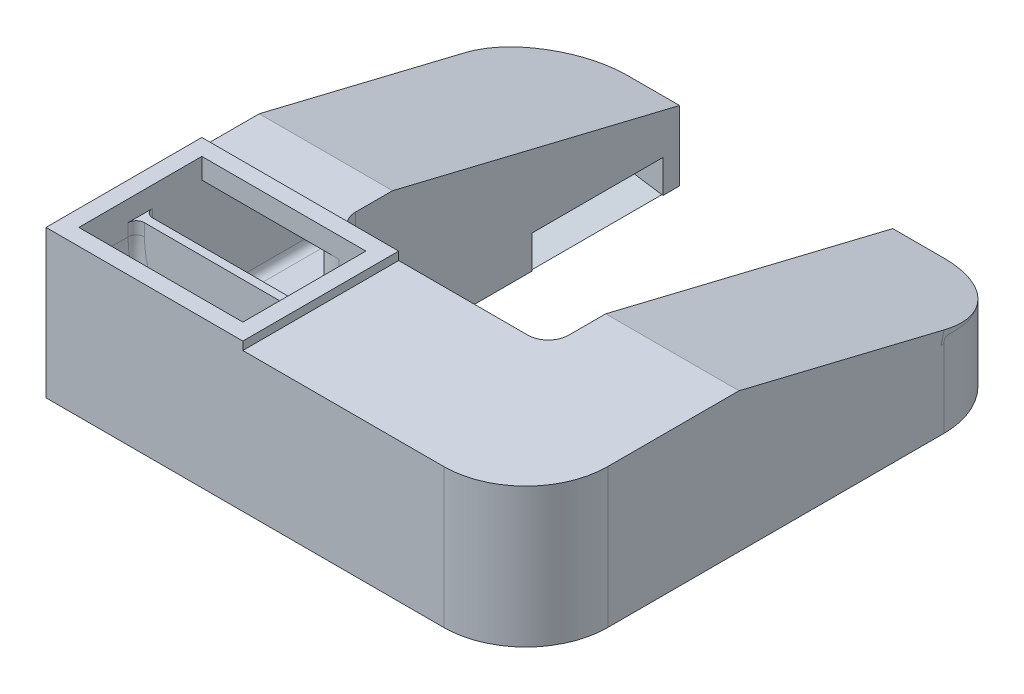
SolidWorks part; units mm, degrees
ref_plane "Front Plane" through (0, 0, 0) normal (0, 0, 1) x (1, 0, 0)
ref_plane "Top Plane" through (0, 0, 0) normal (0, 1, 0) x (1, 0, 0)
ref_plane "Right Plane" through (0, 0, 0) normal (1, 0, 0) x (0, 0, -1)
sketch "Sketch1" plane through (0, 0, 0) normal (0, 1, 0) x (1, 0, 0)
  line L0 (-13, 42) -> (-13, 0)
  line L1 (-13, 0) -> (13, 0)
  line L2 (13, 0) -> (13, 42)
  line L3 (13, 42) -> (19.25, 42)
  line L4 (29.25, 32) -> (29.25, -9)
  line L5 (19.25, -19) -> (-29.25, -19)
  line L6 (-29.25, -19) -> (-29.25, 32)
  line L7 (-19.25, 42) -> (-13, 42)
  arc A0 (19.25, 42) -> (29.25, 32) centre (19.25, 32) cw
  arc A1 (-29.25, 32) -> (-19.25, 42) centre (-19.25, 32) cw
  arc A2 (29.25, -9) -> (19.25, -19) centre (19.25, -9) cw
  point P11 (29.25, 42)
  point P14 (-29.25, 42)
  dimension "D7" = 10
  dimension "D8" = 10
  dimension "D1" = 26
  dimension "D2" = 13
  dimension "D3" = 42
  dimension "D4" = 16.25
  dimension "D5" = 16.25
  dimension "D6" = 19
extrude "Boss-Extrude1" add sketch "Sketch1" along normal blind 2
sketch "Sketch2" plane through (0, 2, 0) normal (0, 1, 0) x (1, 0, 0)
  line L0 (-29.25, 32) -> (-29.25, -19)
  line L1 (-29.25, -19) -> (19.25, -19)
  line L2 (-19.25, 42) -> (-13, 42)
  line L3 (-13, 42) -> (-13, 0)
  line L4 (-13, 0) -> (13, 0)
  line L5 (13, 0) -> (13, 42)
  line L6 (13, 42) -> (19.25, 42)
  line L7 (29.25, 32) -> (29.25, -9)
  line L8 (27.25, 32) -> (27.25, -9)
  line L9 (-27.25, -17) -> (19.25, -17)
  line L10 (-27.25, 32) -> (-27.25, -17)
  line L11 (-19.25, 40) -> (-15, 40)
  line L12 (-15, 40) -> (-15, -2)
  line L13 (-15, -2) -> (15, -2)
  line L14 (15, -2) -> (15, 40)
  line L15 (15, 40) -> (19.25, 40)
  arc A0 (-19.25, 42) -> (-29.25, 32) centre (-19.25, 32) ccw
  arc A1 (19.25, -19) -> (29.25, -9) centre (19.25, -9) ccw
  arc A2 (19.25, 42) -> (29.25, 32) centre (19.25, 32) cw
  arc A3 (19.25, 40) -> (27.25, 32) centre (19.25, 32) cw
  arc A4 (19.25, -17) -> (27.25, -9) centre (19.25, -9) ccw
  arc A5 (-19.25, 40) -> (-27.25, 32) centre (-19.25, 32) ccw
  dimension "D1" = 2
extrude "Boss-Extrude2" add sketch "Sketch2" along normal blind 15
sketch "Sketch3" plane through (0, 2, 0) normal (0, 1, 0) x (1, 0, 0)
  line L0 (-27.25, 32) -> (-27.25, -17) construction
  line L1 (-27.25, -9) -> (-7.25, -9)
  line L11 (15, -2) -> (-15, -2) construction
  line L15 (-7.25, -9) -> (-7.25, -2)
  line L16 (-27.25, -10) -> (-6.25, -10)
  line L18 (-7.25, -2) -> (15, -2)
  line L19 (-27.25, -9) -> (-27.25, -10)
  line L21 (-6.25, -10) -> (7, -10)
  line L23 (-27.25, -17) -> (19.25, -17) construction
  arc A0 (15, -2) -> (7, -10) centre (7, -2) cw
  dimension "D1" = 20
  dimension "D2" = 7
  dimension "D4" = 1
  dimension "D5" = 1
extrude "Boss-Extrude3" add sketch "Sketch3" along normal up to surface (15 mm away) up to face at (1.9383, 17, -17.0065)
fillet "Fillet1" radius 7 2 edges at (-7.25, 2, 5.5) (-17.25, 2, 9)
fillet "Fillet9" radius 12 1 edges at (-27.25, 2, 13.5)
fillet "Fillet6" radius 2.5 2 edges at (13, 8.5, 0) (-13, 8.5, 0)
fillet "Fillet7" radius 4.5 1 edges at (-15, 9.5, 2)
fillet "Fillet8" radius 1 22 edges at (-7.25, 13, 2) (-8.1161, 5.6273, 2) (-12.9756, 2.117, 1.2579) (12.6569, 2, 7.6569) (15, 2, -19) (17.125, 2, -40) (24.9069, 2, -37.6569) (27.25, 2, -11.5) (24.9069, 2, 14.6569) (2, 2, 17) (-4.125, 2, 10) (-24.9069, 2, -37.6569) (-17.125, 2, -40) (-15, 2, -21.25) (-14.8084, 2, -1.201) (-27.25, 2, -15) (-27.25, 15.5, 17) (-23.7353, 5.5147, 17) (-27.25, 15.5, 10) (-23.7353, 5.5147, 10) (-27.25, 13, 9) (-27.25, 4.0503, 6.9497)
sketch "Sketch4" plane through (0, 17, 0) normal (0, 1, 0) x (1, 0, 0)
  line L1 (-10.5, -2) -> (-27.25, -2)
  line L2 (-7.25, -10) -> (-7.25, -17)
  line L3 (-26.25, -17) -> (19.25, -17) construction
  line L6 (-15, 2.5) -> (-15, 40)
  line L7 (-15, 40) -> (-19.25, 40)
  line L8 (-27.25, 32) -> (-27.25, -2)
  line L9 (-7.25, -17) -> (19.25, -17)
  line L10 (27.25, -9) -> (27.25, 32)
  line L11 (19.25, 40) -> (15, 40)
  line L12 (15, 40) -> (15, -2)
  line L13 (7, -10) -> (-7.25, -10)
  line L14 (-26.25, -10) -> (7, -10) construction
  line L15 (-7.25, -3) -> (-7.25, -9) construction
  arc A1 (7, -10) -> (15, -2) centre (7, -2) ccw
  arc A2 (-19.25, 40) -> (-27.25, 32) centre (-19.25, 32) ccw
  arc A3 (19.25, 40) -> (27.25, 32) centre (19.25, 32) cw
  arc A4 (19.25, -17) -> (27.25, -9) centre (19.25, -9) ccw
  arc A6 (-15, 2.5) -> (-10.5, -2) centre (-10.5, 2.5) ccw
  arc A7 (-13.5682, -0.7918) -> (-10.5, -2) centre (-10.5, 2.5) ccw construction
extrude "Boss-Extrude4" add sketch "Sketch4" against normal blind 1.5
sketch "Sketch5" plane through (0, 17, 0) normal (0, 1, 0) x (1, 0, 0)
  line L0 (19.25, -17) -> (-15.25, -17) construction
  line L1 (-27.25, -2) -> (-7.25, -2)
  line L2 (-27.25, -2) -> (-27.25, -17)
  line L3 (-27.25, -17) -> (-7.25, -17)
  line L4 (-7.25, -2) -> (-7.25, -17)
  line L5 (-7.25, -10) -> (-7.25, -17) construction
extrude "Cut-Extrude1" cut sketch "Sketch5" against normal blind 1.5
sketch "Sketch6" plane through (0, 17, 0) normal (0, 1, 0) x (1, 0, 0)
  line L0 (-29.25, -19) -> (19.25, -19) construction
  line L1 (-27.25, -17) -> (-7.25, -17)
  line L2 (-27.25, -17) -> (-27.25, -2)
  line L3 (-27.25, -2) -> (-7.25, -2)
  line L4 (-7.25, -17) -> (-7.25, -2)
  line L5 (-5.25, -19) -> (-29.25, -19)
  line L6 (-5.25, -19) -> (-5.25, 0)
  line L7 (-5.25, 0) -> (-29.25, 0)
  line L8 (-29.25, -19) -> (-29.25, 0)
  dimension "D1" = 2
  dimension "D2" = 2
  dimension "D3" = 2
extrude "Boss-Extrude5" add sketch "Sketch6" along normal blind 1
ref_plane "Plane1" through (0, 0, -32) normal (0, 0, -1) x (-1, 0, 0)
sketch "Sketch7" plane through (0, 0, -32) normal (0, 0, -1) x (-1, 0, 0)
  line L0 (-13, 2) -> (0, 0) construction
  line L1 (-13, 0) -> (-13, 17) construction
  line L2 (0, 0) -> (13, 2) construction
  line L3 (13, 17) -> (13, 0) construction
  line L4 (-19.25, 0) -> (-13, 0) construction
  line L5 (10.5, 0) -> (13, 0) construction
  line L6 (19.25, 0) -> (29.25, 0) construction
  line L7 (26.1529, 2) -> (8.6205, -0.6973)
  line L8 (8.6205, -0.6973) -> (8.0123, 3.2562)
  line L9 (8.0123, 3.2562) -> (25.5447, 5.9535)
  line L10 (25.5447, 5.9535) -> (26.1529, 2)
  dimension "D1" = 2
  dimension "D2" = 2
  dimension "D3" = 2
  dimension "D4" = 4
  dimension "D5" = 2
extrude "Cut-Extrude2" cut sketch "Sketch7" against normal blind 8
sketch "Sketch9" plane through (-13, 0, 0) normal (1, 0, 0) x (0, 0, -1)
  line L0 (7, 17) -> (42, 8.5)
  line L1 (2.5, 17) -> (42, 17) construction
  line L2 (42, 17) -> (42, 0) construction
  line L3 (42, 8.5) -> (42, 17)
  line L4 (42, 17) -> (7, 17)
  dimension "D1" = 35
extrude "Cut-Extrude3" cut sketch "Sketch9" against normal through all
sketch "Sketch10" plane through (0, 17.6585, -4.2885) normal (0, 0.9718, -0.236) x (1, 0, 0)
  line L0 (-29.25, 28.517) -> (-29.25, 2.7903)
  line L1 (-29.25, 2.7903) -> (-13, 2.7903)
  line L2 (-13, 2.7903) -> (-13, 38.8077)
  line L3 (-13, 2.7903) -> (-13, 38.8077) construction
  line L4 (-13, 38.8077) -> (-19.25, 38.8077)
  line L5 (-13, 38.8077) -> (-13, 40.8137) construction
  arc A1 (-19.25, 38.8077) -> (-29.25, 28.517) centre (-19.1047, 28.6623) ccw
  ellipse E0 centre (-19.25, 28.517) end of major axis (-19.25, 38.8077) minor radius 10 (-19.25, 38.8077) -> (-29.25, 28.517) ccw construction
extrude "Boss-Extrude6" add sketch "Sketch10" against normal blind 1.5
sketch "Sketch11" plane through (-0.3041, -1.9767, 0) normal (0.1521, 0.9884, 0) x (0.9884, -0.1521, 0)
  line L0 (-27.3893, 32) -> (-12.8488, 32)
  line L1 (-19.3893, 40) -> (-12.8488, 40)
  line L2 (-12.8488, 32) -> (-12.8488, 40)
  line L3 (-19.4823, 40) -> (-15.2817, 40) construction
  arc A0 (-27.3893, 32) -> (-19.3893, 40) centre (-19.3893, 32) cw
extrude "Cut-Extrude4" cut sketch "Sketch11" along normal blind 4
mirror "Mirror2" about plane through (0, 0, 0) normal (1, 0, 0) of "Cut-Extrude4", "Boss-Extrude6", "Cut-Extrude3", "Cut-Extrude2"
